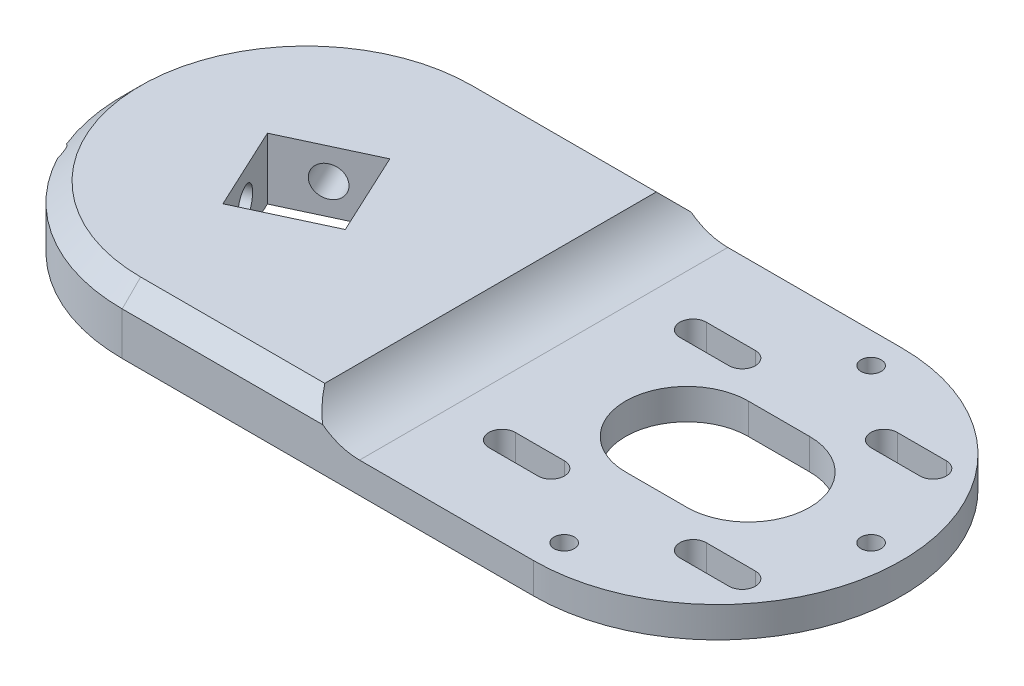
SolidWorks part; units mm, degrees
material "6063-O"
ref_plane "Front Plane" through (0, 0, 0) normal (0, 0, 1) x (1, 0, 0)
ref_plane "Top Plane" through (0, 0, 0) normal (0, 1, 0) x (1, 0, 0)
ref_plane "Right Plane" through (0, 0, 0) normal (1, 0, 0) x (0, 0, -1)
sketch "Sketch1" plane through (0, 0, 0) normal (0, 1, 0) x (1, 0, 0)
  line L0 (-33.5, 0) -> (33.5, 0) construction
  line L1 (-33.5, 30) -> (33.5, 30)
  line L2 (-33.5, -30) -> (33.5, -30)
  line L3 (28.5, 0) -> (38.5, 0) construction
  line L4 (28.5, 10) -> (38.5, 10)
  line L5 (28.5, -10) -> (38.5, -10)
  arc A0 (-33.5, 30) -> (-33.5, -30) centre (-33.5, 0) ccw
  arc A1 (33.5, -30) -> (33.5, 30) centre (33.5, 0) ccw
  arc A2 (28.5, 10) -> (28.5, -10) centre (28.5, 0) ccw
  circle A3 centre (33.5, 0) radius 13.5 construction
  arc A4 (38.5, -10) -> (38.5, 10) centre (38.5, 0) ccw
  point P10 (33.5, 0)
  dimension "D2" = 60
  dimension "D3" = 60
  dimension "D4" = 10
  dimension "D5" = 27
  dimension "D1" = 67
  dimension "D6" = 10
extrude "Boss-Extrude1" add sketch "Sketch1" along normal blind 5
sketch "Sketch2" plane through (0, 5, 0) normal (0, 1, 0) x (1, 0, 0)
  line L0 (13.9437, 15.5563) -> (21.9437, 15.5563) construction
  line L1 (13.9437, 17.7063) -> (21.9437, 17.7063)
  line L2 (13.9437, 13.4063) -> (21.9437, 13.4063)
  line L3 (33.5, 0) -> (33.5, 22) construction
  line L4 (17.9437, 15.5563) -> (33.5, 0) construction
  line L5 (11.5, 0) -> (55.5, 0) construction
  line L6 (53.0563, 15.5563) -> (45.0563, 15.5563) construction
  line L7 (53.0563, 17.7063) -> (45.0563, 17.7063)
  line L8 (53.0563, 13.4063) -> (45.0563, 13.4063)
  line L9 (53.0563, -15.5563) -> (45.0563, -15.5563) construction
  line L10 (53.0563, -17.7063) -> (45.0563, -17.7063)
  line L11 (53.0563, -13.4063) -> (45.0563, -13.4063)
  line L12 (13.9437, -15.5563) -> (21.9437, -15.5563) construction
  line L13 (13.9437, -17.7063) -> (21.9437, -17.7063)
  line L14 (13.9437, -13.4063) -> (21.9437, -13.4063)
  circle A0 centre (33.5, 0) radius 22 construction
  arc A1 (13.9437, 17.7063) -> (13.9437, 13.4063) centre (13.9437, 15.5563) ccw
  arc A2 (21.9437, 13.4063) -> (21.9437, 17.7063) centre (21.9437, 15.5563) ccw
  arc A3 (53.0563, 17.7063) -> (53.0563, 13.4063) centre (53.0563, 15.5563) cw
  arc A4 (45.0563, 13.4063) -> (45.0563, 17.7063) centre (45.0563, 15.5563) cw
  arc A5 (53.0563, -17.7063) -> (53.0563, -13.4063) centre (53.0563, -15.5563) ccw
  arc A6 (45.0563, -13.4063) -> (45.0563, -17.7063) centre (45.0563, -15.5563) ccw
  arc A7 (13.9437, -17.7063) -> (13.9437, -13.4063) centre (13.9437, -15.5563) cw
  arc A8 (21.9437, -13.4063) -> (21.9437, -17.7063) centre (21.9437, -15.5563) cw
  arc A9 (33.5, -30) -> (33.5, 30) centre (33.5, 0) ccw construction
  point P5 (17.9437, 15.5563)
  point P16 (49.0563, 15.5563)
  point P23 (49.0563, -15.5563)
  point P30 (17.9437, -15.5563)
  dimension "D1" = 44
  dimension "D3" = 2.15
  dimension "D2" = 8
  dimension "D4" = 45
extrude "Cut-Extrude1" cut sketch "Sketch2" against normal through all
sketch "Sketch6" plane through (0, 0, 0) normal (0, -1, 0) x (-1, 0, 0)
  circle A0 centre (-33.5, 0) radius 26 construction
  arc A2 (-33.5, 30) -> (-33.5, -30) centre (-33.5, 0) ccw construction
  dimension "D1" = 52
sketch "Sketch8" plane through (0, 5, 0) normal (0, 1, 0) x (1, 0, 0)
  line L0 (-3.5, 30) -> (-3.5, -30)
  line L1 (33.5, 30) -> (-33.5, 30) construction
  line L2 (-33.5, -30) -> (33.5, -30) construction
  line L3 (-3.5, 30) -> (-33.5, 30)
  line L4 (-3.5, -30) -> (-33.5, -30)
  circle A0 centre (-33.5, 0) radius 30
  arc A1 (-33.5, 30) -> (-33.5, -30) centre (-33.5, 0) ccw construction
  line M6 (33.5, 30) -> (-33.5, 30)
  arc M7 (-33.5, 30) -> (-33.5, -30) centre (-33.5, 0) ccw
  line M8 (-33.5, -30) -> (33.5, -30)
  dimension "D1" = 60
extrude "Boss-Extrude2" add sketch "Sketch8" along normal blind 5 contours A0 M7 | A0 L0 M6 | A0 L0 M8 region at (-10.201, 5, -23.299) region at (-33.5, 5, 0) region at (-10.201, 5, 23.299)
fillet "Fillet1" radius 10 1 edges
sketch "Sketch9" plane through (0, 10, 0) normal (0, 1, 0) x (1, 0, 0)
  line L0 (-3.5, 0) -> (-63.5, 0) construction
  line L1 (-3.5, 30) -> (-3.5, -30) construction
  line L3 (-23.5331, -3.6277) -> (-37.1277, -9.9669)
  line L4 (-37.1277, -9.9669) -> (-43.4669, 3.6277)
  line L5 (-43.4669, 3.6277) -> (-29.8723, 9.9669)
  line L6 (-29.8723, 9.9669) -> (-23.5331, -3.6277)
  line L7 (-37.1277, -9.9669) -> (-29.8723, 9.9669) construction
  line L9 (-23.5331, -3.6277) -> (-43.4669, 3.6277) construction
  arc A0 (-33.5, 30) -> (-33.5, -30) centre (-33.5, 0) ccw construction
  point P15 (-33.5, 0)
  dimension "D5" = 30
  dimension "D1" = 65
  dimension "D3" = 15
extrude "Cut-Extrude2" cut sketch "Sketch9" against normal through all contours L6 L5 L4 L3 region at (-33.5, 10, 0)
hole_wizard "M4 Tapped Hole1" positions "Sketch12" profile "Sketch11" tap size "M4" standard "DIN" end condition through all
sketch "Sketch12" plane through (0, 5, 0) normal (0, 1, 0) x (1, 0, 0)
  line L0 (58.5, 0) -> (8.5, 0) construction
  line L3 (33.5, 25) -> (33.5, -25) construction
  circle A0 centre (33.5, 0) radius 25 construction
  arc A2 (33.5, -30) -> (33.5, 30) centre (33.5, 0) ccw construction
  point P6 (58.5, 0)
  point P11 (33.5, 25)
  point P12 (33.5, -25)
  dimension "D1" = 50
sketch "Sketch11" plane through (58.5, 5, 0) normal (1, 0, 0) x (0, 0, 1)
  line L0 (0, 0) -> (0, 5)
  line L1 (0, 5) -> (1.65, 5)
  line L2 (1.65, 5) -> (1.65, 0)
  line L5 (1.65, 0) -> (0, 0)
  line L11 (0, -6.35) -> (0, 107.95) construction
  dimension "Thru Tap Drill Dia." = 3.3
  dimension "Thru Tap Drill Depth" = 5
cosmetic thread "Hole Thread8" parameters "D2"=4
cosmetic thread "Hole Thread9" parameters "D2"=4
cosmetic thread "Hole Thread10" parameters "D2"=4
hole_wizard "M6 Tapped Hole1" positions "Sketch14" profile "Sketch13" tap size "M6" standard "DIN" end condition through all
sketch "Sketch14" plane through (-34.314, 0, 16.0009) normal (0.9063, 0, -0.4226) x (-0.4226, 0, -0.9063)
  line L0 (21.6577, 10) -> (6.6577, 0) construction
  line L3 (21.6577, 0) -> (6.6577, 10) construction
  line L4 (6.6577, 0) -> (21.6577, 0) construction
  line L6 (21.6577, 0) -> (21.6577, 10) construction
  line L7 (6.6577, 0) -> (6.6577, 10) construction
  line L8 (6.6577, 10) -> (21.6577, 10) construction
  line L9 (6.6577, 0) -> (21.6577, 0) construction
  point P18 (14.1577, 5)
sketch "Sketch13" plane through (-40.2973, 5, 3.1696) normal (0, 1, 0) x (-0.4226, 0, -0.9063)
  line L0 (0, 0) -> (0, 32.3678)
  line L1 (0, 32.3678) -> (2.5, 32.3678)
  line L2 (2.5, 32.3678) -> (2.5, 0)
  line L5 (2.5, 0) -> (0, 0)
  line L11 (0, -6.35) -> (0, 107.95) construction
  dimension "Thru Tap Drill Dia." = 5
  dimension "Thru Tap Drill Depth" = 32.3678
cosmetic thread "Hole Thread11" parameters "D2"=6
hole_wizard "M6 Tapped Hole3" positions "3DSketch2" profile "Sketch17" tap size "M6" standard "DIN" end condition through all
sketch3d "3DSketch2"
  line L0 (-29.8723, 10, -9.9669) -> (-43.4669, 0, -3.6277) construction
  line L3 (-43.4669, 10, -3.6277) -> (-29.8723, 0, -9.9669) construction
  point P0 (-36.6696, 5, -6.7973)
sketch "Sketch17" plane through (-36.6696, 5, -6.7973) normal (0, 1, 0) x (0.9063, 0, -0.4226)
  line L0 (0, 0) -> (0, 32.3678)
  line L1 (0, 32.3678) -> (2.5, 32.3678)
  line L2 (2.5, 32.3678) -> (2.5, 0)
  line L5 (2.5, 0) -> (0, 0)
  line L11 (0, -6.35) -> (0, 107.95) construction
  dimension "Thru Tap Drill Dia." = 5
  dimension "Thru Tap Drill Depth" = 32.3678
cosmetic thread "Hole Thread12" parameters "D1"=22.5, "D2"=6
chamfer "Chamfer1" distance 3 angle 45 3 edges at (-18.5, 10, 30) (-63.5, 10, 0) (-18.5, 10, -30)
